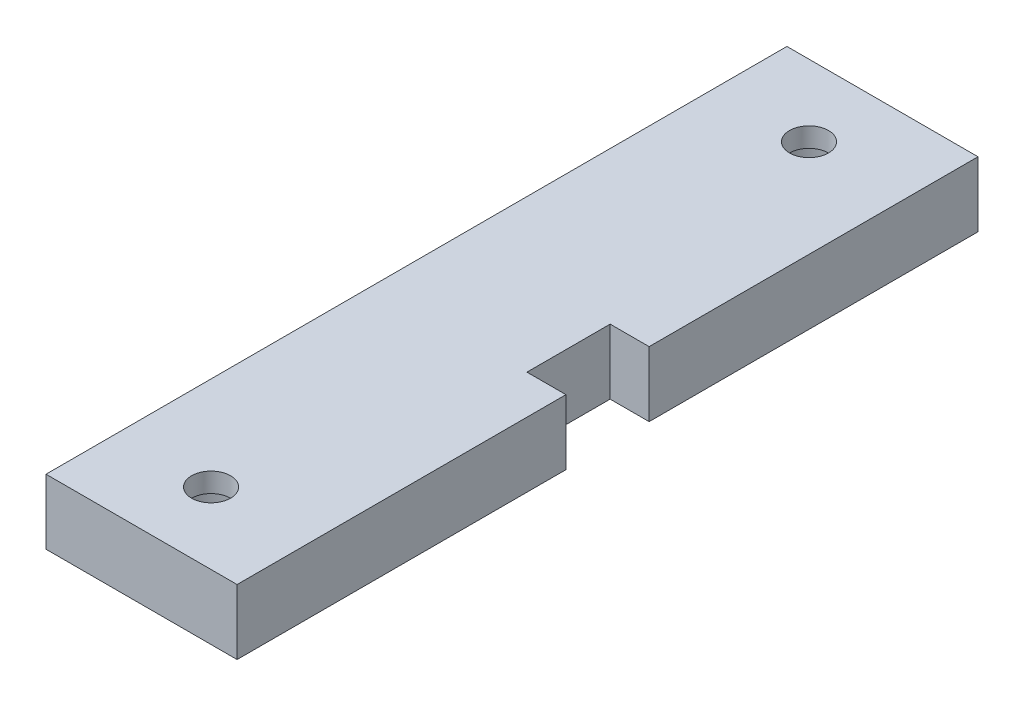
SolidWorks part; units mm, degrees
ref_plane "Front" through (0, 0, 0) normal (0, 0, 1) x (1, 0, 0)
ref_plane "Top" through (0, 0, 0) normal (0, 1, 0) x (1, 0, 0)
ref_plane "Right" through (0, 0, 0) normal (1, 0, 0) x (0, 0, -1)
sketch "草图2" plane through (0, 0, 0) normal (0, 1, 0) x (1, 0, 0)
  line L0 (-22.4307, -42.4706) -> (-1.4307, -42.4706)
  line L1 (-22.4307, -42.4706) -> (-22.4307, 14.5294)
  line L2 (-22.4307, 14.5294) -> (-1.4307, 14.5294)
  line L3 (-1.4307, 14.5294) -> (-1.4307, -42.4706)
extrude "凸台-拉伸1" add sketch "草图2" along normal blind 5 contours L3 L0 L1 L2
sketch "草图3" plane through (0, 5, 0) normal (0, 1, 0) x (1, 0, 0)
  line L0 (-1.4307, -42.4706) -> (-1.4307, -31.4706)
  line L1 (-1.4307, 14.5294) -> (-1.4307, -42.4706) construction
  line L2 (-1.4307, -31.4706) -> (-22.4307, -42.4706)
  circle A0 centre (-11.9307, -36.9706) radius 1.5
extrude "切除-拉伸1" cut sketch "草图3" against normal blind 5 contours L2 A0 | L2 A0 region at (-11.6353, 5, 37.5345) region at (-12.2261, 5, 36.4066)
sketch "草图4" plane through (0, 5, 0) normal (0, 1, 0) x (1, 0, 0)
  line L0 (-22.4307, 14.5294) -> (-22.4307, 3.5294)
  line L1 (-22.4307, -42.4706) -> (-22.4307, 14.5294) construction
  line L2 (-22.4307, 3.5294) -> (-1.4307, 14.5294)
  circle A0 centre (-11.9307, 9.0294) radius 1.5
extrude "切除-拉伸2" cut sketch "草图4" against normal blind 5 contours L2 A0 | L2 A0 region at (-12.2261, 5, -9.5934) region at (-11.6353, 5, -8.4655)
sketch "草图5" plane through (0, 0, 0) normal (0, -1, 0) x (1, 0, 0)
  circle A0 centre (-11.9307, -9.0294) radius 3.5
extrude "切除-拉伸3" cut sketch "草图5" against normal blind 3.5
sketch "草图6" plane through (0, 0, 0) normal (0, -1, 0) x (1, 0, 0)
  circle A0 centre (-11.9307, 36.9706) radius 3.5
extrude "切除-拉伸4" cut sketch "草图6" against normal blind 3.5
ref_plane "基准面1" through (-22.4307, 0, 42.4706) normal (1, 0, 0) x (0, 0, -1)
sketch "草图8" plane through (0, 5, 0) normal (0, 1, 0) x (1, 0, 0)
  line L0 (-22.4307, 14.5294) -> (-19.4307, 14.5294)
  line L1 (-22.4307, 14.5294) -> (-1.4307, 14.5294) construction
  line L2 (-19.4307, 14.5294) -> (-19.4307, -42.4706)
  line L3 (-22.4307, -42.4706) -> (-1.4307, -42.4706) construction
  line L4 (-19.4307, -42.4706) -> (-22.4307, -42.4706)
  line L5 (-22.4307, -42.4706) -> (-22.4307, 14.5294)
  line L6 (-11.9307, 14.5294) -> (-11.9307, -42.4706) construction
  line L7 (-4.4307, -42.4706) -> (-1.4307, -42.4706)
  line L8 (-4.4307, 14.5294) -> (-4.4307, -42.4706)
  line L9 (-1.4307, 14.5294) -> (-4.4307, 14.5294)
  line L10 (-1.4307, -42.4706) -> (-1.4307, 14.5294)
extrude "切除-拉伸5" cut sketch "草图8" against normal blind 5
sketch "草图10" plane through (0, 5, 0) normal (0, 1, 0) x (1, 0, 0)
  line L0 (-19.4307, -13.9706) -> (-4.4307, -13.9706) construction
  line L1 (-19.4307, -42.4706) -> (-19.4307, 14.5294) construction
  line L2 (-4.4307, 14.5294) -> (-4.4307, -42.4706) construction
  line L3 (-4.4307, -13.9706) -> (-4.4307, -10.9706)
  line L4 (-4.4307, -10.9706) -> (-7.4307, -10.9706)
  line L5 (-7.4307, -10.9706) -> (-7.4307, -16.9706)
  line L6 (-7.4307, -16.9706) -> (-4.4307, -16.9706)
  line L7 (-4.4307, -16.9706) -> (-4.4307, -13.9706)
extrude "切除-拉伸7" cut sketch "草图10" against normal blind 5 contours L7 L3 L4 L5 L6
sketch "草图11" plane through (0, 0, 0) normal (0, -1, 0) x (1, 0, 0)
  line L0 (-19.4307, 13.9706) -> (-7.4307, 13.9706) construction
  line L1 (-19.4307, 42.4706) -> (-19.4307, -14.5294) construction
  line L2 (-7.4307, 10.9706) -> (-7.4307, 16.9706) construction
  line L3 (-19.4307, 13.9706) -> (-19.4307, 1.4706)
  line L4 (-19.4307, 1.4706) -> (-4.4307, 1.4706)
  line L6 (-4.4307, -14.5294) -> (-4.4307, 10.9706) construction
  line L8 (-19.4307, 42.4706) -> (-19.1307, 42.4706)
  line L9 (-19.4307, 42.4706) -> (-4.4307, 42.4706) construction
  line L10 (-19.1307, 42.4706) -> (-19.1307, -14.5294)
  line L11 (-19.4307, -14.5294) -> (-4.4307, -14.5294) construction
  line L12 (-19.1307, -14.5294) -> (-19.4307, -14.5294)
  line L13 (-19.4307, -14.5294) -> (-19.4307, 42.4706)
  line M3 (-4.4307, 42.4706) -> (-19.4307, 42.4706)
  line M4 (-19.4307, 42.4706) -> (-19.4307, -14.5294)
extrude "切除-拉伸8" cut sketch "草图11" against normal blind 5 contours L0 L10 M4 M3 region at (-19.2807, 0, 28.2206)
sketch "草图12" plane through (0, 0, 0) normal (0, -1, 0) x (-1, 0, 0)
  line L0 (19.4307, -13.9706) -> (19.4307, 14.5294)
  line L1 (19.4307, 14.5294) -> (19.1307, 14.5294)
  line L2 (19.4307, 14.5294) -> (4.4307, 14.5294) construction
  line L3 (19.1307, 14.5294) -> (19.1307, -13.9706)
  line L4 (19.1307, -13.9706) -> (19.4307, -13.9706)
extrude "切除-拉伸9" cut sketch "草图12" against normal blind 10
sketch "草图13" plane through (0, 0, 0) normal (0, -1, 0) x (1, 0, 0)
  line L0 (-4.4307, 10.9706) -> (-4.4307, 10.7706)
  line L1 (-4.4307, -14.5294) -> (-4.4307, 10.9706) construction
  line L2 (-4.4307, 10.7706) -> (-7.4307, 10.7706)
  line L3 (-7.4307, 10.7706) -> (-7.4307, 10.9706)
  line L4 (-7.4307, 10.9706) -> (-4.4307, 10.9706)
  line L5 (-7.4307, 16.9706) -> (-4.4307, 16.9706)
  line L7 (-7.4307, 16.9706) -> (-7.4307, 17.1706)
  line L8 (-4.4307, 16.9706) -> (-4.4307, 17.1706)
  line L9 (-4.4307, 16.9706) -> (-4.4307, 42.4706) construction
  line L10 (-4.4307, 17.1706) -> (-7.4307, 17.1706)
  line M11 (-4.4307, -14.5294) -> (-4.4307, 10.9706)
  line M12 (-4.4307, 10.9706) -> (-7.4307, 10.9706)
extrude "切除-拉伸10" cut sketch "草图13" against normal blind 10 contours L3 L2 M11 M12 | L4 L0 L2 L3 | L5 L8 L10 L7 region at (-5.9307, 0, 10.8706)
